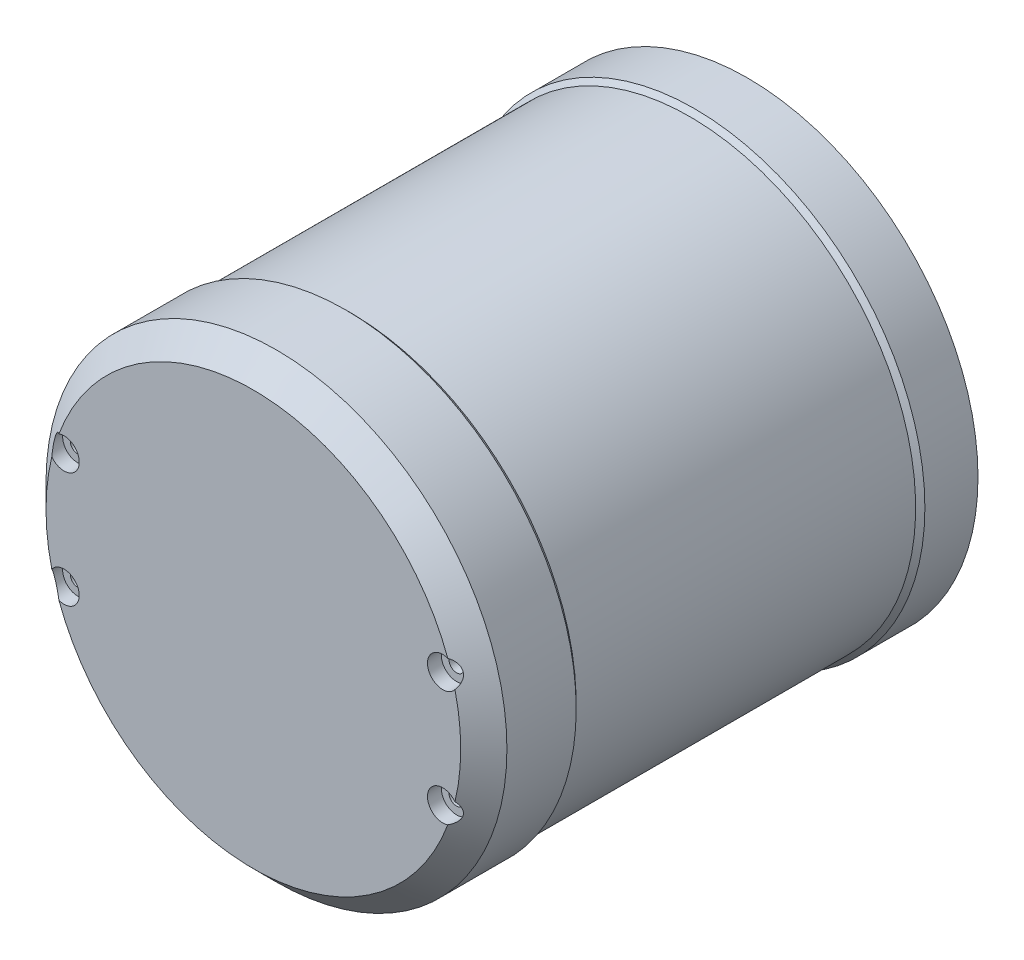
SolidWorks part; units mm, degrees
ref_plane "Front Plane" through (0, 0, 0) normal (0, 0, 1) x (1, 0, 0)
ref_plane "Top Plane" through (0, 0, 0) normal (0, 1, 0) x (1, 0, 0)
ref_plane "Right Plane" through (0, 0, 0) normal (1, 0, 0) x (0, 0, -1)
sketch "Sketch1" plane through (0, 0, 0) normal (0, 0, 1) x (1, 0, 0)
  circle A1 centre (0, 55) radius 47.5
  circle A2 centre (0, 55) radius 49.9
  circle A3 centre (0, 55) radius 49.9
  arc A4 (-37, 84.306) -> (-37, 25.694) centre (0, 55) ccw construction
  dimension "D2" = 0.3
  dimension "D1" = 0.3
extrude "Boss-Extrude1" add sketch "Sketch1" against normal up to surface (100 mm away)
sketch "Sketch2" plane through (0, 0, 0) normal (0, 0, 1) x (1, 0, 0)
  circle A0 centre (0, 55) radius 49.9 construction
  circle A1 centre (0, 55) radius 49.9
  circle A2 centre (41, 67.5) radius 1.65
  circle A3 centre (41, 42.5) radius 1.65
  circle A4 centre (-41, 67.5) radius 1.65
  circle A5 centre (-41, 42.5) radius 1.65
  circle A6 centre (41, 67.5) radius 2.25 construction
  circle A7 centre (41, 42.5) radius 2.25 construction
  circle A8 centre (-41, 67.5) radius 2.25 construction
  circle A9 centre (-41, 42.5) radius 2.25 construction
  dimension "D1" = 3.3
extrude "Boss-Extrude2" add sketch "Sketch2" along normal blind 7
sketch "Sketch3" plane through (0, 0, 7) normal (0, 0, 1) x (1, 0, 0)
  circle A0 centre (-41, 67.5) radius 3.3
  circle A1 centre (-41, 42.5) radius 3.3
  circle A2 centre (41, 67.5) radius 3.3
  circle A3 centre (41, 42.5) radius 3.3
  dimension "D1" = 6.6
extrude "Cut-Extrude1" cut sketch "Sketch3" against normal blind 3
chamfer "Chamfer1" distance 5 angle 45 1 edges at (49.9, 55, 7)
sketch "Sketch4" plane through (0, 0, 0) normal (1, 0, 0) x (0, 0, -1)
  line L0 (88.5, 88.7868) -> (88.5, 0) construction
  line L1 (88.5, 88.7868) -> (88.5, 0) construction
  line L2 (-2, 5.1) -> (-2, 104.9) construction
  line L3 (-2, 5.1) -> (-2, 104.9) construction
  line L4 (-2, 55) -> (-50002, 55) construction
  line L5 (13, 104.9) -> (14, 103.9)
  line L6 (100, 104.9) -> (-2, 104.9) construction
  line L7 (14, 103.9) -> (87.5, 103.9)
  line L8 (87.5, 103.9) -> (88.5, 104.9)
  line L9 (13, 104.9) -> (88.5, 104.9)
  point P6 (-2, 55)
  dimension "D1" = 135
  dimension "D2" = 135
  dimension "D3" = 15
  dimension "D4" = 1
revolve "Cut-Revolve1" cut sketch "Sketch4" angle 360 about L4
sketch "Sketch5" plane through (0, 0, -100) normal (0, 0, -1) x (-1, 0, 0)
  circle A0 centre (-44, 45) radius 3.3
  circle A1 centre (-44, 65) radius 3.3
  circle A2 centre (44, 45) radius 3.3
  circle A3 centre (44, 65) radius 3.3
  dimension "D1" = 6.6
extrude "Cut-Extrude2" cut sketch "Sketch5" against normal blind 8
